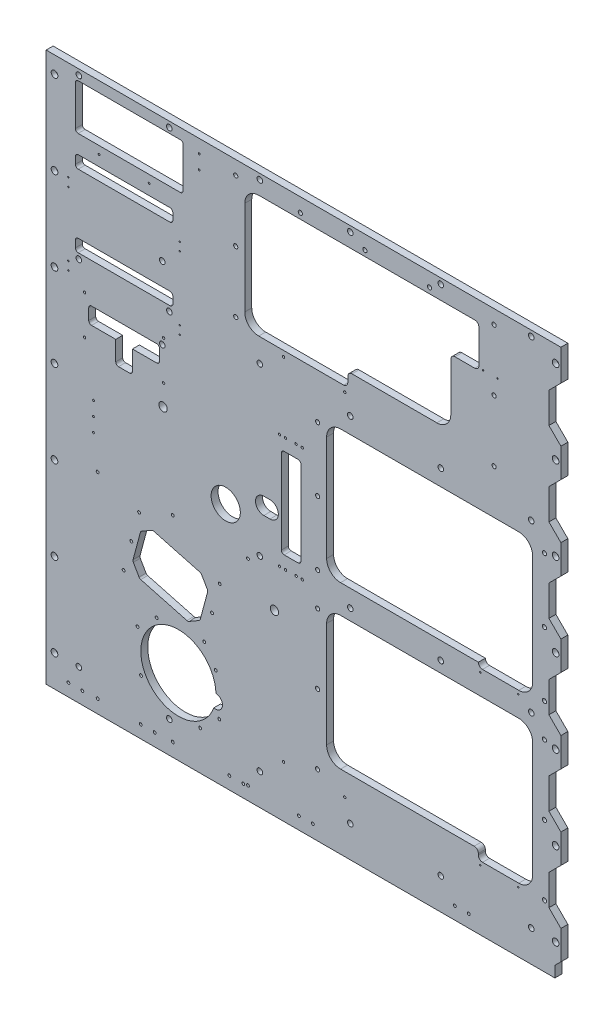
SolidWorks part; units mm, degrees
ref_plane "前视基准面" through (0, 0, 0) normal (0, 0, 1) x (1, 0, 0)
ref_plane "上视基准面" through (0, 0, 0) normal (0, 1, 0) x (1, 0, 0)
ref_plane "右视基准面" through (0, 0, 0) normal (1, 0, 0) x (0, 0, -1)
sketch "草图1" plane through (0, 0, 0) normal (0, 0, 1) x (1, 0, 0)
  line L1 (-924.5, 986.5) -> (924.5, 986.5)
  line L2 (-924.5, 986.5) -> (-924.5, -986.5)
  line L3 (-924.5, -986.5) -> (924.5, -986.5)
  line L4 (924.5, 986.5) -> (924.5, -986.5)
  line L5 (-924.5, 986.5) -> (924.5, -986.5) construction
  line L6 (-924.5, -986.5) -> (924.5, 986.5) construction
  point P0 (0, 0)
  dimension "D1" = 1973
  dimension "D2" = 1849
base flange "基体-法兰1" sketch "草图1" thickness 25 reverse thickness direction no parameters "D1"=1
sketch "草图6" plane through (0, 0, 0) normal (0, 0, 1) x (1, 0, 0)
  line L0 (924.5, 874.5) -> (881.5, 831.5)
  line L1 (924.5, -986.5) -> (924.5, 986.5) construction
  line L2 (881.5, 831.5) -> (881.5, 721.5)
  line L3 (881.5, 721.5) -> (924.5, 678.5)
  line L4 (924.5, 574.5) -> (881.5, 531.5)
  line L5 (881.5, 531.5) -> (881.5, 421.5)
  line L6 (881.5, 421.5) -> (924.5, 378.5)
  line L7 (924.5, 274.5) -> (881.5, 231.5)
  line L8 (881.5, 231.5) -> (881.5, 121.5)
  line L9 (881.5, 121.5) -> (924.5, 78.5)
  line L10 (924.5, -25.5) -> (881.5, -68.5)
  line L11 (881.5, -68.5) -> (881.5, -178.5)
  line L12 (881.5, -178.5) -> (924.5, -221.5)
  line L13 (924.5, -325.5) -> (881.5, -368.5)
  line L14 (881.5, -368.5) -> (881.5, -478.5)
  line L15 (881.5, -478.5) -> (924.5, -521.5)
  line L16 (924.5, -625.5) -> (881.5, -668.5)
  line L17 (881.5, -668.5) -> (881.5, -778.5)
  line L18 (881.5, -778.5) -> (924.5, -821.5)
  line L19 (924.5, 986.5) -> (-924.5, 986.5) construction
  line L20 (924.5, -925.5) -> (903, -947)
  line L21 (903, -947) -> (903, -986.5)
  line L22 (-924.5, -986.5) -> (924.5, -986.5) construction
  line L23 (924.5, -925.5) -> (924.5, -986.5)
  line L24 (924.5, -986.5) -> (903, -986.5)
  line L25 (924.5, -821.5) -> (924.5, -625.5)
  line L26 (924.5, -521.5) -> (924.5, -325.5)
  line L27 (924.5, -221.5) -> (924.5, -25.5)
  line L28 (924.5, 78.5) -> (924.5, 274.5)
  line L29 (924.5, 378.5) -> (924.5, 574.5)
  line L30 (924.5, 678.5) -> (924.5, 874.5)
  dimension "D1" = 112
  dimension "D2" = 43
  dimension "D3" = 155
  dimension "D4" = 110
  dimension "D5" = 104
  dimension "D6" = 190
  dimension "D7" = 110
  dimension "D8" = 43
  dimension "D9" = 190
  dimension "D10" = 110
  dimension "D11" = 110
  dimension "D12" = 110
  dimension "D13" = 110
  dimension "D14" = 104
  dimension "D15" = 104
  dimension "D16" = 190
  dimension "D17" = 104
  dimension "D18" = 190
  dimension "D19" = 104
  dimension "D20" = 190
  dimension "D21" = 43
  dimension "D22" = 21.5
  dimension "D23" = 104
  dimension "D24" = 39.5
extrude "切除-拉伸2" cut sketch "草图6" against normal through all normal cut yes
sketch "草图8" plane through (0, 0, 0) normal (0, 0, 1) x (1, 0, 0)
  line L0 (924.5, 874.5) -> (924.5, 986.5) construction
  line L1 (924.5, 986.5) -> (-924.5, 986.5) construction
  line L2 (-924.5, 986.5) -> (-924.5, -986.5) construction
  circle A0 centre (905.5, 926.5) radius 12
  circle A1 centre (905.5, 626.5) radius 12
  circle A2 centre (905.5, 326.5) radius 12
  circle A3 centre (905.5, 26.5) radius 12
  circle A4 centre (905.5, -273.5) radius 12
  circle A5 centre (905.5, -573.5) radius 12
  circle A6 centre (905.5, -873.5) radius 12
  circle A7 centre (-894.5, 926.5) radius 12
  circle A8 centre (-894.5, 626.5) radius 12
  circle A9 centre (-894.5, 326.5) radius 12
  circle A10 centre (-894.5, 26.5) radius 12
  circle A11 centre (-894.5, -273.5) radius 12
  circle A12 centre (-894.5, -573.5) radius 12
  circle A13 centre (-894.5, -873.5) radius 12
  point P17 (924.5, 930.5)
  dimension "D1" = 19
  dimension "D2" = 24
  dimension "D3" = 24
  dimension "D4" = 24
  dimension "D5" = 24
  dimension "D6" = 24
  dimension "D7" = 24
  dimension "D8" = 24
  dimension "D9" = 60
  dimension "D10" = 300
  dimension "D11" = 300
  dimension "D12" = 300
  dimension "D13" = 300
  dimension "D15" = 300
  dimension "D16" = 60
  dimension "D17" = 300
  dimension "D18" = 300
  dimension "D19" = 300
  dimension "D20" = 300
  dimension "D21" = 300
  dimension "D22" = 24
  dimension "D23" = 24
  dimension "D24" = 24
  dimension "D25" = 24
  dimension "D26" = 24
  dimension "D27" = 24
  dimension "D28" = 30
  dimension "D29" = 300
  dimension "D30" = 24
  dimension "D14" = 300
extrude "切除-拉伸3" cut sketch "草图8" against normal blind 16 normal cut yes
sketch "草图10" plane through (0, 0, 0) normal (0, 0, 1) x (1, 0, 0)
  line L0 (-924.5, 986.5) -> (-924.5, -986.5) construction
  line L1 (924.5, 986.5) -> (-924.5, 986.5) construction
  circle A0 centre (-807, 966.5) radius 10
  circle A1 centre (-482, 966.5) radius 10
  circle A2 centre (-157, 966.5) radius 10
  circle A3 centre (168, 966.5) radius 10
  circle A4 centre (493, 966.5) radius 10
  circle A5 centre (818, 966.5) radius 10
  circle A6 centre (-807, 394.5) radius 10
  circle A7 centre (493, 394.5) radius 10
  circle A8 centre (818, 394.5) radius 10
  circle A9 centre (168, 394.5) radius 10
  circle A10 centre (-157, 394.5) radius 10
  circle A11 centre (-482, 394.5) radius 10
  circle A12 centre (818, -203.5) radius 10
  circle A14 centre (493, -203.5) radius 10
  circle A15 centre (-157, -203.5) radius 10
  circle A16 centre (168, -203.5) radius 10
  circle A18 centre (818, -873.5) radius 10
  circle A19 centre (-482, -873.5) radius 10
  circle A20 centre (-807, -873.5) radius 10
  circle A21 centre (-157, -873.5) radius 10
  circle A22 centre (168, -873.5) radius 10
  circle A23 centre (493, -873.5) radius 10
  dimension "D1" = 325
  dimension "D2" = 325
  dimension "D3" = 325
  dimension "D4" = 325
  dimension "D5" = 325
  dimension "D6" = 117.5
  dimension "D7" = 20
  dimension "D8" = 20
  dimension "D9" = 20
  dimension "D10" = 20
  dimension "D11" = 20
  dimension "D12" = 20
  dimension "D13" = 20
  dimension "D14" = 20
  dimension "D15" = 20
  dimension "D16" = 20
  dimension "D17" = 20
  dimension "D18" = 20
  dimension "D19" = 20
  dimension "D20" = 20
  dimension "D21" = 20
  dimension "D22" = 20
  dimension "D23" = 20
  dimension "D24" = 20
  dimension "D25" = 20
  dimension "D26" = 325
  dimension "D27" = 325
  dimension "D28" = 20
  dimension "D29" = 20
  dimension "D30" = 20
  dimension "D31" = 20
  dimension "D32" = 572
  dimension "D34" = 670
  dimension "D35" = 325
  dimension "D36" = 117.5
  dimension "D38" = 325
  dimension "D39" = 325
  dimension "D41" = 325
  dimension "D42" = 325
  dimension "D43" = 325
  dimension "D44" = 325
  dimension "D45" = 325
  dimension "D46" = 325
  dimension "D47" = 325
  dimension "D48" = 117.5
  dimension "D33" = 598
  dimension "D37" = 325
  dimension "D40" = 325
extrude "切除-拉伸5" cut sketch "草图10" against normal blind 16 normal cut yes
sketch "草图9" plane through (0, 0, 0) normal (0, 0, 1) x (1, 0, 0)
  circle A0 centre (905.5, 926.5) radius 7
  circle A1 centre (905.5, 626.5) radius 7
  circle A2 centre (905.5, 326.5) radius 7
  circle A3 centre (905.5, 26.5) radius 7
  circle A4 centre (905.5, -273.5) radius 7
  circle A5 centre (905.5, -573.5) radius 7
  circle A6 centre (905.5, -873.5) radius 7
  circle A7 centre (-894.5, 926.5) radius 7
  circle A8 centre (-894.5, 626.5) radius 7
  circle A9 centre (-894.5, 326.5) radius 7
  circle A10 centre (-894.5, 26.5) radius 7
  circle A11 centre (-894.5, -273.5) radius 7
  circle A12 centre (-894.5, -573.5) radius 7
  circle A13 centre (-894.5, -873.5) radius 7
  circle A14 centre (818, 966.5) radius 5.25
  circle A15 centre (493, 966.5) radius 5.25
  circle A16 centre (168, 966.5) radius 5.25
  circle A17 centre (-157, 966.5) radius 5.25
  circle A18 centre (-482, 966.5) radius 5.25
  circle A19 centre (-807, 966.5) radius 5.25
  circle A20 centre (-807, 394.5) radius 5.25
  circle A21 centre (-482, 394.5) radius 5.25
  circle A22 centre (-157, 394.5) radius 5.25
  circle A23 centre (168, 394.5) radius 5.25
  circle A24 centre (493, 394.5) radius 5.25
  circle A25 centre (818, 394.5) radius 5.25
  circle A26 centre (818, -203.5) radius 5.25
  circle A27 centre (493, -203.5) radius 5.25
  circle A28 centre (168, -203.5) radius 5.25
  circle A29 centre (-157, -203.5) radius 5.25
  circle A30 centre (-807, -873.5) radius 5.25
  circle A31 centre (-482, -873.5) radius 5.25
  circle A32 centre (-157, -873.5) radius 5.25
  circle A33 centre (168, -873.5) radius 5.25
  circle A34 centre (493, -873.5) radius 5.25
  circle A35 centre (818, -873.5) radius 5.25
  dimension "D1" = 14
  dimension "D2" = 14
  dimension "D3" = 14
  dimension "D4" = 14
  dimension "D5" = 14
  dimension "D6" = 14
  dimension "D7" = 14
  dimension "D8" = 14
  dimension "D9" = 14
  dimension "D10" = 14
  dimension "D11" = 14
  dimension "D12" = 14
  dimension "D13" = 14
  dimension "D14" = 14
  dimension "D15" = 10.5
  dimension "D16" = 10.5
  dimension "D17" = 10.5
  dimension "D18" = 10.5
  dimension "D19" = 10.5
  dimension "D20" = 10.5
  dimension "D21" = 10.5
  dimension "D22" = 10.5
  dimension "D23" = 10.5
  dimension "D24" = 10.5
  dimension "D25" = 10.5
  dimension "D26" = 10.5
  dimension "D27" = 10.5
  dimension "D28" = 10.5
  dimension "D29" = 10.5
  dimension "D30" = 10.5
  dimension "D31" = 10.5
  dimension "D32" = 10.5
  dimension "D33" = 10.5
  dimension "D34" = 10.5
  dimension "D35" = 10.5
  dimension "D36" = 10.5
extrude "切除-拉伸4" cut sketch "草图9" against normal through all normal cut yes
sketch "草图11" plane through (0, 0, 0) normal (0, 0, 1) x (1, 0, 0)
  line L0 (-644.5, -280.615) -> (-644.5, 1050.9989) construction
  line L1 (-924.5, 986.5) -> (-924.5, -986.5) construction
  line L2 (-517.5, 271.5) -> (-771.5, 271.5)
  line L3 (-819.5, 948.5) -> (-432.5, 948.5)
  line L4 (-819.5, 948.5) -> (-819.5, 784.5)
  line L5 (-819.5, 784.5) -> (-432.5, 784.5)
  line L6 (-432.5, 948.5) -> (-432.5, 784.5)
  line L7 (-819.5, 718.5) -> (-469.5, 718.5)
  line L8 (-819.5, 718.5) -> (-819.5, 673.5)
  line L9 (-819.5, 673.5) -> (-469.5, 673.5)
  line L10 (-469.5, 718.5) -> (-469.5, 673.5)
  line L11 (-819.5, 458.5) -> (-469.5, 458.5)
  line L12 (-819.5, 458.5) -> (-819.5, 413.5)
  line L13 (-819.5, 413.5) -> (-469.5, 413.5)
  line L14 (-469.5, 458.5) -> (-469.5, 413.5)
  line L15 (-771.5, 271.5) -> (-771.5, 211.5)
  line L16 (-771.5, 211.5) -> (-674.5, 211.5)
  line L17 (-674.5, 211.5) -> (-674.5, 131.5)
  line L18 (-674.5, 131.5) -> (-614.5, 131.5)
  line L19 (-614.5, 211.5) -> (-614.5, 131.5)
  line L20 (-517.5, 211.5) -> (-614.5, 211.5)
  line L21 (-517.5, 271.5) -> (-517.5, 211.5)
  line L22 (924.5, 986.5) -> (-924.5, 986.5) construction
  line L23 (-211, 916.5) -> (630, 916.5)
  line L24 (630, 916.5) -> (630, 766.5)
  line L25 (630, 766.5) -> (529, 766.5)
  line L26 (529, 766.5) -> (529, 528.5)
  line L27 (529, 528.5) -> (159, 528.5)
  line L28 (-211, 478.5) -> (-211, 916.5)
  line L29 (159, 528.5) -> (159, 478.5)
  line L30 (159, 478.5) -> (-211, 478.5)
  line L31 (83, -141.5) -> (628, -141.5)
  line L32 (83, 336.5) -> (823, 336.5)
  line L33 (83, 336.5) -> (83, -141.5)
  line L34 (628, -141.5) -> (628, -156.5)
  line L35 (823, 336.5) -> (823, -156.5)
  line L36 (83, -243.5) -> (823, -243.5)
  line L37 (83, -243.5) -> (83, -721.5)
  line L38 (628, -156.5) -> (823, -156.5)
  line L39 (823, -243.5) -> (823, -756.5)
  line L40 (83, -721.5) -> (628, -721.5)
  line L41 (628, -721.5) -> (628, -756.5)
  line L42 (628, -756.5) -> (823, -756.5)
  line L43 (-924.5, -986.5) -> (903, -986.5) construction
  line L44 (924.5, -925.5) -> (924.5, -821.5) construction
  line L45 (-449.5, -763.5) -> (-449.5, -280.615) construction
  line L46 (-79.5, 165.5) -> (-9.5, 165.5)
  line L47 (-79.5, 165.5) -> (-79.5, -156.5)
  line L48 (-79.5, -156.5) -> (-9.5, -156.5)
  line L49 (-9.5, 165.5) -> (-9.5, -156.5)
  line L50 (-142.5, -40.5) -> (-120.5, -40.5) construction
  line L51 (-142.5, -10.5) -> (-120.5, -10.5)
  line L52 (-142.5, -70.5) -> (-120.5, -70.5)
  line L53 (-634.6101, -713.5) -> (-251.5936, -713.5) construction
  line L54 (-286.0589, -757.2939) -> (-642.6336, -661.75) construction
  line L55 (-584.2881, -397.8591) -> (-147.8754, -514.7955) construction
  line L56 (-496.2324, -887.9078) -> (-388.5239, -485.934) construction
  line L57 (-771.1894, -662.5494) -> (-210.6051, -751.3372) construction
  line L58 (-457.3794, -347.6496) -> (-495.9438, -491.5738) construction
  line L59 (-334.3986, -371.6419) -> (-575.8801, -306.9371)
  line L60 (-575.8801, -306.9371) -> (-622.4675, -480.8038)
  line L61 (-622.4675, -480.8038) -> (-380.9861, -545.5085)
  line L62 (-334.3986, -371.6419) -> (-380.9861, -545.5085)
  circle A0 centre (-243.5, 936.5) radius 7.5
  circle A1 centre (-243.5, 716.5) radius 7.5
  circle A2 centre (-243.5, 496.5) radius 7.5
  circle A3 centre (-11.5, 936.5) radius 7.5
  circle A4 centre (220.5, 936.5) radius 7.5
  circle A5 centre (452.5, 936.5) radius 7.5
  circle A6 centre (684.5, 936.5) radius 7.5
  circle A7 centre (684.5, 716.5) radius 7.5
  circle A8 centre (684.5, 496.5) radius 7.5
  circle A9 centre (-374.5, 938.5) radius 3.4
  circle A10 centre (-374.5, 888.5) radius 3.4
  circle A11 centre (-734.5, 756.5) radius 3.4
  circle A12 centre (-554.5, 756.5) radius 3.4
  circle A13 centre (-507.5, 538.5) radius 10
  circle A14 centre (-507.5, 278.5) radius 10
  circle A15 centre (-844.5, 630.5) radius 2.55
  circle A16 centre (-844.5, 600.5) radius 2.55
  circle A17 centre (-844.5, 370.5) radius 2.55
  circle A18 centre (-844.5, 340.5) radius 2.55
  circle A19 centre (-444.5, 340.5) radius 2.55
  circle A20 centre (-444.5, 370.5) radius 2.55
  circle A21 centre (-444.5, 600.5) radius 2.55
  circle A22 centre (-444.5, 630.5) radius 2.55
  circle A23 centre (-786.5, 301.5) radius 4.25
  circle A24 centre (-786.5, 161.5) radius 4.25
  circle A25 centre (-502.5, 161.5) radius 4.25
  circle A26 centre (-502.5, 301.5) radius 4.25
  circle A27 centre (-504.5, 86.5) radius 15
  circle A28 centre (-754.5, -18.5) radius 3.4
  circle A29 centre (-754.5, -68.5) radius 3.4
  circle A30 centre (-754.5, -118.5) radius 3.4
  circle A31 centre (645, 775) radius 2.55
  circle A32 centre (697, 775) radius 2.55
  circle A33 centre (50.5, 316.5) radius 7.5
  circle A34 centre (865.5, 316.5) radius 7.5
  circle A35 centre (865.5, 86.5) radius 7.5
  circle A36 centre (865.5, -263.5) radius 7.5
  circle A37 centre (50.5, 86.5) radius 7.5
  circle A38 centre (50.5, -263.5) radius 7.5
  circle A39 centre (50.5, -143.5) radius 7.5
  circle A40 centre (50.5, -763.5) radius 7.5
  circle A41 centre (50.5, -513.5) radius 7.5
  circle A42 centre (865.5, -143.5) radius 7.5
  circle A43 centre (865.5, -763.5) radius 7.5
  circle A44 centre (865.5, -513.5) radius 7.5
  circle A45 centre (-72, 458.5) radius 4.25
  circle A46 centre (148, 458.5) radius 4.25
  circle A47 centre (635, -170) radius 2.55
  circle A48 centre (771, -170) radius 2.55
  circle A49 centre (635, -770) radius 2.55
  circle A50 centre (771, -770) radius 2.55
  circle A51 centre (593.5, -941.5) radius 5.15
  circle A52 centre (543.5, -941.5) radius 5.15
  circle A53 centre (-16.5, -941.5) radius 5.15
  circle A54 centre (33.5, -941.5) radius 5.15
  circle A55 centre (-266.5, -941.5) radius 5.15
  circle A56 centre (-216.5, -941.5) radius 5.15
  circle A57 centre (-844.5, -941.5) radius 5.15
  circle A58 centre (-584.5, -941.5) radius 5.15
  circle A59 centre (-534.5, -941.5) radius 5.15
  circle A60 centre (-794.5, -941.5) radius 5.15
  circle A61 centre (148, -801.5) radius 4.25
  circle A62 centre (-72, -801.5) radius 4.25
  circle A63 centre (-86.5, 209.5) radius 4.25
  circle A64 centre (-64.5, 209.5) radius 4.25
  circle A65 centre (-26.5, 209.5) radius 4.25
  circle A66 centre (-4.5, 209.5) radius 4.25
  circle A67 centre (-86.5, -200.5) radius 4.25
  circle A68 centre (-64.5, -200.5) radius 4.25
  circle A69 centre (-4.5, -200.5) radius 4.25
  circle A70 centre (-26.5, -200.5) radius 4.25
  arc A71 (-142.5, -10.5) -> (-142.5, -70.5) centre (-142.5, -40.5) ccw
  arc A72 (-120.5, -70.5) -> (-120.5, -10.5) centre (-120.5, -40.5) ccw
  circle A73 centre (-104.5, -346.5) radius 15
  arc A74 (-314.5543, -709.6704) -> (-322.3425, -758.8427) centre (-449.5, -713.5) ccw
  circle A75 centre (-739.5, -938.5) radius 5.15
  circle A76 centre (-469.5, -938.5) radius 5.15
  circle A77 centre (-199.5, -938.5) radius 5.15
  circle A78 centre (-739.5, -233.5) radius 5.15
  circle A79 centre (-469.5, -233.5) radius 5.15
  circle A80 centre (-199.5, -233.5) radius 5.15
  circle A81 centre (-279.5, -103.5) radius 52.5
  circle A82 centre (-527.9288, -581.1929) radius 5.15
  circle A83 centre (-596.2836, -643.1112) radius 5.15
  circle A84 centre (-583.5749, -788.8669) radius 5.15
  circle A85 centre (-371.0712, -845.8071) radius 5.15
  circle A86 centre (-287.1873, -725.9333) radius 5.15 construction
  circle A87 centre (-315.4251, -638.1331) radius 5.15
  arc A88 (-322.3425, -758.8427) -> (-314.5543, -709.6704) centre (-316.1621, -734.6187) ccw
  circle A89 centre (-590.6693, -284.8571) radius 5.15
  circle A90 centre (-300.8915, -362.5028) radius 5.15
  circle A91 centre (-356.5376, -570.1768) radius 5.15
  circle A92 centre (-646.3154, -492.5311) radius 5.15
  circle A93 centre (-328.7146, -466.3398) radius 5.15
  circle A94 centre (-618.4923, -388.6941) radius 5.15
  circle A95 centre (-302.7164, -783.8888) radius 5.15
  circle A96 centre (-611.8127, -701.0667) radius 5.15 construction
  point P23 (-644.5, 131.5)
  point P26 (-644.5, 271.5)
  point P202 (-131.5, -40.5)
  point P256 (-501.7268, -513.1562)
  point P257 (-455.1394, -339.2895)
  dimension "D19" = 401
  dimension "D20" = 928
  dimension "D21" = 220
  dimension "D22" = 220
  dimension "D23" = 232
  dimension "D24" = 232
  dimension "D25" = 232
  dimension "D26" = 15
  dimension "D27" = 15
  dimension "D28" = 15
  dimension "D29" = 15
  dimension "D30" = 15
  dimension "D31" = 15
  dimension "D32" = 15
  dimension "D33" = 15
  dimension "D34" = 15
  dimension "D44" = 6.8
  dimension "D45" = 6.8
  dimension "D46" = 48
  dimension "D47" = 50
  dimension "D48" = 131
  dimension "D49" = 180
  dimension "D50" = 6.8
  dimension "D52" = 135
  dimension "D53" = 260
  dimension "D54" = 20
  dimension "D55" = 20
  dimension "D56" = 137
  dimension "D57" = 126
  dimension "D58" = 30
  dimension "D59" = 230
  dimension "D60" = 30
  dimension "D61" = 5.1
  dimension "D62" = 5.1
  dimension "D63" = 5.1
  dimension "D64" = 5.1
  dimension "D65" = 400
  dimension "D66" = 39
  dimension "D67" = 140
  dimension "D68" = 284
  dimension "D69" = 8.5
  dimension "D70" = 8.5
  dimension "D71" = 45
  dimension "D72" = 140
  dimension "D73" = 30
  dimension "D74" = 180
  dimension "D75" = 50
  dimension "D76" = 50
  dimension "D77" = 110
  dimension "D78" = 6.8
  dimension "D79" = 6.8
  dimension "D80" = 6.8
  dimension "D81" = 52
  dimension "D82" = 15
  dimension "D84" = 5.1
  dimension "D85" = 5.1
  dimension "D91" = 294
  dimension "D92" = 32.5
  dimension "D93" = 15
  dimension "D94" = 815
  dimension "D95" = 620
  dimension "D96" = 15
  dimension "D97" = 15
  dimension "D98" = 15
  dimension "D99" = 15
  dimension "D100" = 15
  dimension "D101" = 15
  dimension "D102" = 15
  dimension "D103" = 15
  dimension "D104" = 15
  dimension "D105" = 15
  dimension "D106" = 15
  dimension "D108" = 230
  dimension "D109" = 230
  dimension "D110" = 120
  dimension "D111" = 250
  dimension "D112" = 250
  dimension "D113" = 20
  dimension "D115" = 220
  dimension "D116" = 8.5
  dimension "D117" = 8.5
  dimension "D122" = 28.5
  dimension "D123" = 5.1
  dimension "D124" = 5.1
  dimension "D125" = 136
  dimension "D127" = 5.1
  dimension "D128" = 5.1
  dimension "D130" = 50
  dimension "D131" = 10.3
  dimension "D132" = 10.3
  dimension "D133" = 45
  dimension "D134" = 331
  dimension "D135" = 50
  dimension "D136" = 50
  dimension "D137" = 50
  dimension "D138" = 50
  dimension "D139" = 510
  dimension "D140" = 200
  dimension "D141" = 268
  dimension "D142" = 210
  dimension "D143" = 45
  dimension "D144" = 10.3
  dimension "D145" = 10.3
  dimension "D146" = 10.3
  dimension "D147" = 10.3
  dimension "D148" = 10.3
  dimension "D149" = 10.3
  dimension "D150" = 10.3
  dimension "D151" = 10.3
  dimension "D152" = 45
  dimension "D153" = 45
  dimension "D154" = 45
  dimension "D155" = 38
  dimension "D156" = 8.5
  dimension "D157" = 8.5
  dimension "D159" = 220
  dimension "D160" = 22
  dimension "D161" = 22
  dimension "D162" = 38
  dimension "D163" = 195
  dimension "D166" = 7
  dimension "D167" = 777
  dimension "D168" = 44
  dimension "D169" = 8.5
  dimension "D170" = 8.5
  dimension "D171" = 8.5
  dimension "D172" = 8.5
  dimension "D173" = 8.5
  dimension "D174" = 8.5
  dimension "D175" = 8.5
  dimension "D176" = 8.5
  dimension "D177" = 410
  dimension "D179" = 250
  dimension "D181" = 30
  dimension "D183" = 30
  dimension "D184" = 146
  dimension "D185" = 100
  dimension "D186" = 270
  dimension "D188" = 270
  dimension "D189" = 270
  dimension "D191" = 225
  dimension "D192" = 10.3
  dimension "D193" = 10.3
  dimension "D194" = 10.3
  dimension "D195" = 10.3
  dimension "D196" = 10.3
  dimension "D197" = 10.3
  dimension "D198" = 705
  dimension "D201" = 105
  dimension "D202" = 130
  dimension "D203" = 190
  dimension "D204" = 220
  dimension "D205" = 30
  dimension "D206" = 320
  dimension "D207" = 107.5
  dimension "D208" = 107.5
  dimension "D209" = 220
  dimension "D210" = 10.3
  dimension "D211" = 10.3
  dimension "D212" = 10.3
  dimension "D214" = 25
  dimension "D219" = 145
  dimension "D220" = 145
  dimension "D221" = 155
  dimension "D222" = 155
  dimension "D223" = 215
  dimension "D224" = 215
  dimension "D225" = 10.3
  dimension "D226" = 10.3
  dimension "D227" = 10.3
  dimension "D228" = 10.3
  dimension "D229" = 30
  dimension "D230" = 10.3
  dimension "D231" = 320
  dimension "D1" = 280
  dimension "D2" = 175
  dimension "D3" = 212
  dimension "D4" = 38
  dimension "D5" = 164
  dimension "D6" = 175
  dimension "D7" = 175
  dimension "D8" = 66
  dimension "D9" = 45
  dimension "D10" = 215
  dimension "D11" = 45
  dimension "D12" = 175
  dimension "D13" = 175
  dimension "D14" = 142
  dimension "D15" = 60
  dimension "D16" = 80
  dimension "D17" = 60
  dimension "D18" = 254
  dimension "D35" = 50
  dimension "D36" = 841
  dimension "D37" = 238
  dimension "D38" = 50
  dimension "D39" = 32.5
  dimension "D40" = 101
  dimension "D41" = 370
  dimension "D42" = 438
  dimension "D43" = 70
  dimension "D51" = 230
  dimension "D83" = 141.5
  dimension "D86" = 740
  dimension "D87" = 740
  dimension "D88" = 478
  dimension "D89" = 102
  dimension "D90" = 142
  dimension "D107" = 478
  dimension "D114" = 65
  dimension "D118" = 35
  dimension "D119" = 195
  dimension "D120" = 195
  dimension "D121" = 15
  dimension "D126" = 52
  dimension "D129" = 48.5
  dimension "D158" = 65
  dimension "D164" = 445
  dimension "D165" = 70
  dimension "D178" = 322
  dimension "D180" = 45
  dimension "D182" = 22
  dimension "D187" = 1700
  dimension "D190" = 20
  dimension "D199" = 15
  dimension "D200" = 270
  dimension "D213" = 6
  dimension "D215" = 102.3
  dimension "D216" = 250
  dimension "D217" = 90
  dimension "D218" = 90
extrude "切除-拉伸6" cut sketch "草图11" against normal through all normal cut yes
fillet "圆角1" radius 10 18 edges at (-517.5, 271.5, -12.5) (-517.5, 211.5, -12.5) (-614.5, 131.5, -12.5) (-771.5, 271.5, -12.5) (-771.5, 211.5, -12.5) (-674.5, 131.5, -12.5) (-469.5, 413.5, -12.5) (-819.5, 413.5, -12.5) (-819.5, 458.5, -12.5) (-469.5, 458.5, -12.5) (-819.5, 673.5, -12.5) (-819.5, 718.5, -12.5) (-469.5, 673.5, -12.5) (-469.5, 718.5, -12.5) (-819.5, 784.5, -12.5) (-432.5, 784.5, -12.5) (-432.5, 948.5, -12.5) (-819.5, 948.5, -12.5)
fillet "圆角2" radius 50 3 edges at (529, 528.5, -12.5) (-211, 478.5, -12.5) (-211, 916.5, -12.5)
fillet "圆角3" radius 15 5 edges at (630, 916.5, -12.5) (630, 766.5, -12.5) (529, 766.5, -12.5) (159, 528.5, -12.5) (159, 478.5, -12.5)
fillet "圆角4" radius 50 8 edges at (823, -756.5, -12.5) (823, -243.5, -12.5) (83, -721.5, -12.5) (83, -243.5, -12.5) (83, -141.5, -12.5) (823, -156.5, -12.5) (823, 336.5, -12.5) (83, 336.5, -12.5)
fillet "圆角5" radius 15 3 edges at (628, -156.5, -12.5) (628, -756.5, -12.5) (628, -721.5, -12.5)
fillet "圆角6" radius 10 4 edges at (-79.5, -156.5, -12.5) (-9.5, -156.5, -12.5) (-9.5, 165.5, -12.5) (-79.5, 165.5, -12.5)
chamfer "倒角1" distance 35 angle 45 4 edges at (-575.8801, -306.9371, -12.5) (-622.4675, -480.8038, -12.5) (-380.9861, -545.5085, -12.5) (-334.3986, -371.6419, -12.5)
fillet "圆角7" radius 10 8 edges at (-542.0727, -315.9958, -12.5) (-584.9388, -340.7445, -12.5) (-613.4088, -446.9964, -12.5) (-588.6601, -489.8624, -12.5) (-414.7935, -536.4499, -12.5) (-371.9274, -511.7011, -12.5) (-343.4573, -405.4493, -12.5) (-368.206, -362.5832, -12.5)
sketch "折弯-线1" plane through (0, 0, 0) normal (0, 1, 0) x (1, 0, 0)
sketch "边界框1" plane through (0, 0, 0) normal (0, 1, 0) x (1, 0, 0)
sheet metal parameters "钣金6" thickness 25 parameters "D1"=1
flat pattern "平板型式6" [suppressed]
sketch "折弯-线2" plane through (0, 0, 0) normal (0, 1, 0) x (1, 0, 0)
sketch "边界框2" [suppressed] plane through (0, 0, 0) normal (0, 1, 0) x (1, 0, 0)
sheet metal parameters "钣金7" thickness 25 parameters "D1"=1
flat pattern "平板型式6"
sketch "折弯-线2" plane through (0, 0, 0) normal (0, 1, 0) x (1, 0, 0)
sketch "边界框2" [suppressed] plane through (0, 0, 0) normal (0, 1, 0) x (1, 0, 0)
sheet metal parameters "钣金8" thickness 25 parameters "D1"=1
flat pattern "平板型式6"
sketch "折弯-线2" plane through (0, 0, 0) normal (0, 1, 0) x (1, 0, 0)
sketch "边界框2" [suppressed] plane through (0, 0, 0) normal (0, 1, 0) x (1, 0, 0)
sheet metal parameters "钣金9" thickness 25 parameters "D1"=1
flat pattern "平板型式6"
sketch "折弯-线2" plane through (0, 0, 0) normal (0, 1, 0) x (1, 0, 0)
sketch "边界框2" [suppressed] plane through (0, 0, 0) normal (0, 1, 0) x (1, 0, 0)
sheet metal parameters "钣金10" thickness 25 parameters "D1"=1
flat pattern "平板型式6"
sketch "折弯-线2" plane through (0, 0, 0) normal (0, 1, 0) x (1, 0, 0)
sketch "边界框2" [suppressed] plane through (0, 0, 0) normal (0, 1, 0) x (1, 0, 0)
sheet metal parameters "钣金11" thickness 25 parameters "D1"=1
flat pattern "平板型式6"
sketch "折弯-线2" plane through (0, 0, 0) normal (0, 1, 0) x (1, 0, 0)
sketch "边界框2" [suppressed] plane through (0, 0, 0) normal (0, 1, 0) x (1, 0, 0)
